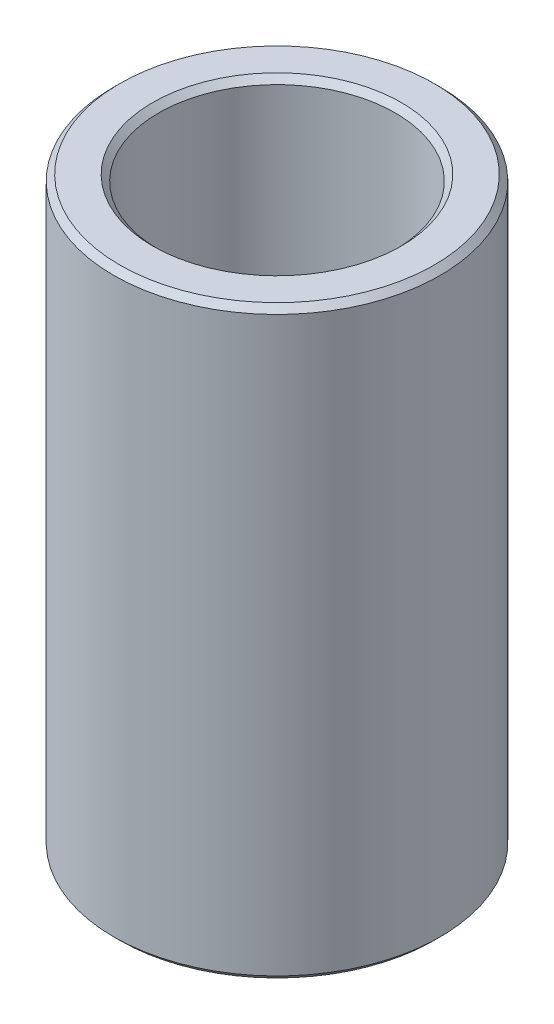
SolidWorks part; units mm, degrees
ref_plane "Front Plane" through (0, 0, 0) normal (0, 0, 1) x (1, 0, 0)
ref_plane "Top Plane" through (0, 0, 0) normal (0, 1, 0) x (1, 0, 0)
ref_plane "Right Plane" through (0, 0, 0) normal (1, 0, 0) x (0, 0, -1)
sketch "Sketch1" plane through (0, 0, 0) normal (0, 1, 0) x (1, 0, 0)
  circle A0 centre (0, 0) radius 25
  dimension "SLEEVE_OD" = 50
extrude "Boss-Extrude1" add sketch "Sketch1" along normal blind 89.5943
sketch "Sketch2" plane through (0, 0, 0) normal (0, 1, 0) x (1, 0, 0)
  circle A0 centre (0, 0) radius 18.1286
  dimension "BORE_D" = 36.2572
extrude "Cut-Extrude1" cut sketch "Sketch2" along normal through all
chamfer "Chamfer1" distance 0.9188 angle 45 4 edges at (0, 89.5943, 18.1286) (0, 0, 18.1286) (0, 0, 25) (0, 89.5943, 25)
